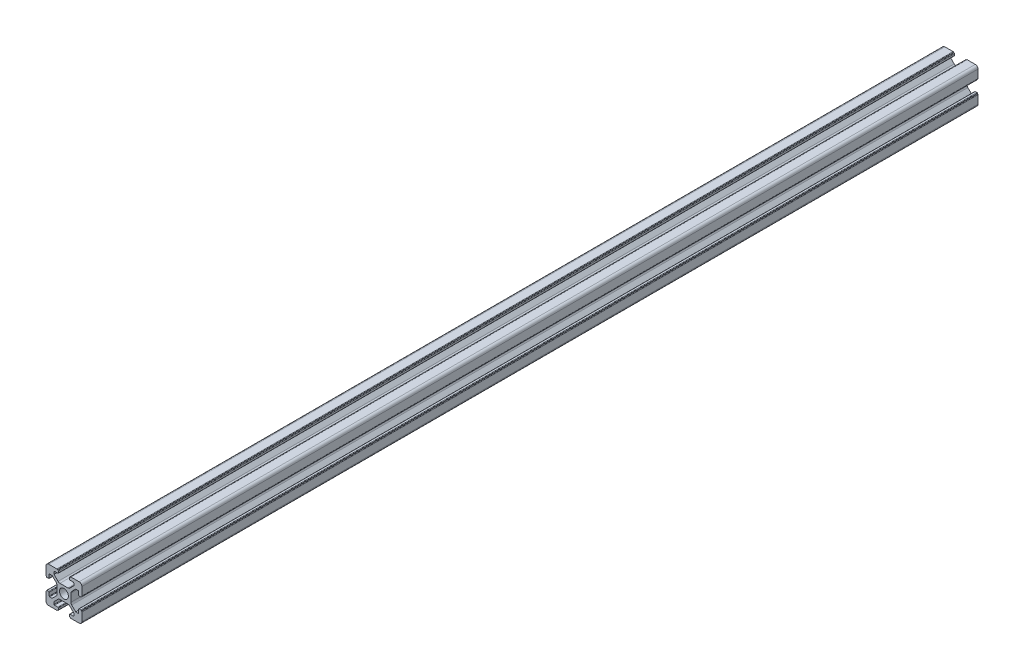
SolidWorks part; units mm, degrees
material "1060 Alloy"
ref_plane "Front Plane" through (0, 0, 0) normal (0, 0, 1) x (1, 0, 0)
ref_plane "Top Plane" through (0, 0, 0) normal (0, 1, 0) x (1, 0, 0)
ref_plane "Right Plane" through (0, 0, 0) normal (1, 0, 0) x (0, 0, -1)
sketch "Sketch1" plane through (0, 0, 0) normal (0, 0, 1) x (1, 0, 0)
  line L0 (3.8995, 3.9005) -> (10.4604, 10.4604) construction
  line L2 (-3.9002, 2.2177) -> (-3.9002, -2.2208)
  line L5 (-3.9005, 3.899) -> (3.9001, -3.8986) construction
  line L6 (-3.9, -3.901) -> (3.8995, 3.9005) construction
  line L7 (-0.0002, 10) -> (-0.0002, -9.9996) construction
  line L8 (-0.0002, -9.9996) -> (-0.0002, 10) construction
  line L9 (5.5006, 6.5619) -> (3.2793, 4.3405)
  line L14 (-10.0002, 9.9996) -> (9.9994, -10) construction
  line L15 (-9.9999, -10.0001) -> (9.9998, 10) construction
  line L16 (6.5613, 5.5012) -> (4.3401, 3.28)
  line L17 (-5.5002, 6.5603) -> (-3.279, 4.3391)
  line L18 (-6.5609, 5.4996) -> (-4.3395, 3.2783)
  line L19 (7.9206, 5.5012) -> (6.5613, 5.5012)
  line L20 (8.2006, 3.3812) -> (8.2006, 5.2212)
  line L21 (9.4206, 3.1012) -> (8.4806, 3.1012)
  line L22 (9.7006, 3.6012) -> (9.7006, 3.3812)
  line L23 (-8.5002, 9.9996) -> (-3.8802, 9.9996)
  line L24 (-3.6002, 9.7196) -> (-3.6002, 9.6996)
  line L25 (-3.6002, 9.6996) -> (-3.3802, 9.6996)
  line L26 (-3.1002, 9.4196) -> (-3.1002, 8.4796)
  line L27 (-3.3802, 8.1996) -> (-5.2202, 8.1996)
  line L28 (-5.5002, 7.9196) -> (-5.5002, 6.5603)
  line L29 (-7.9202, 5.4996) -> (-6.5609, 5.4996)
  line L30 (-8.2002, 3.3796) -> (-8.2002, 5.2196)
  line L31 (-9.4202, 3.0996) -> (-8.4802, 3.0996)
  line L32 (-9.7202, 3.5996) -> (-9.7002, 3.5996)
  line L33 (-9.7002, 3.5996) -> (-9.7002, 3.3796)
  line L34 (-10.0002, 8.4996) -> (-10.0002, 3.8796)
  line L35 (10.0006, 8.5012) -> (10.0006, 3.8812)
  line L36 (8.5006, 10.0012) -> (3.8806, 10.0012)
  line L37 (3.6006, 9.7012) -> (3.3806, 9.7012)
  line L38 (3.1006, 9.4212) -> (3.1006, 8.4812)
  line L39 (3.3806, 8.2012) -> (5.2206, 8.2012)
  line L40 (5.5006, 7.9212) -> (5.5006, 6.5619)
  line L41 (6.5629, -5.4996) -> (4.3415, -3.2783)
  line L42 (5.5022, -6.5603) -> (3.281, -4.3391)
  line L43 (5.5022, -7.9196) -> (5.5022, -6.5603)
  line L44 (3.3822, -8.1996) -> (5.2222, -8.1996)
  line L45 (3.1022, -9.4196) -> (3.1022, -8.4796)
  line L46 (3.6022, -9.6996) -> (3.3822, -9.6996)
  line L47 (8.5022, -9.9996) -> (3.8822, -9.9996)
  line L48 (10.0022, -8.4996) -> (10.0022, -3.8796)
  line L49 (9.7022, -3.5996) -> (9.7022, -3.3796)
  line L50 (9.4222, -3.0996) -> (8.4822, -3.0996)
  line L51 (8.2022, -3.3796) -> (8.2022, -5.2196)
  line L52 (7.9222, -5.4996) -> (6.5629, -5.4996)
  line L53 (-5.4986, -6.5619) -> (-3.2773, -4.3405)
  line L54 (-6.5593, -5.5012) -> (-4.3395, -3.2814)
  line L55 (-7.9186, -5.5012) -> (-6.5593, -5.5012)
  line L56 (-8.1986, -3.3812) -> (-8.1986, -5.2212)
  line L57 (-9.4186, -3.1012) -> (-8.4786, -3.1012)
  line L58 (-9.6986, -3.6012) -> (-9.6986, -3.3812)
  line L59 (-9.9986, -8.5012) -> (-9.9986, -3.8812)
  line L60 (-8.4986, -10.0012) -> (-3.8786, -10.0012)
  line L61 (-3.5986, -9.7012) -> (-3.3786, -9.7012)
  line L62 (-3.0986, -9.4212) -> (-3.0986, -8.4812)
  line L63 (-3.3786, -8.2012) -> (-5.2186, -8.2012)
  line L64 (-5.4986, -7.9212) -> (-5.4986, -6.5619)
  line L65 (-2.233, 3.8998) -> (2.2187, 3.9012)
  line L66 (3.9008, 2.234) -> (3.9022, -2.2177)
  line L67 (2.235, -3.8998) -> (-2.2167, -3.9012)
  line L68 (3.6006, 9.7212) -> (3.6006, 9.6996)
  line L69 (9.7006, 3.6012) -> (9.7206, 3.6012)
  line L70 (-9.6986, -3.6012) -> (-9.7186, -3.6012)
  line L71 (-3.5986, -9.7012) -> (-3.5986, -9.7212)
  line L72 (3.6022, -9.6996) -> (3.6022, -9.7196)
  line L73 (9.7222, -3.5996) -> (9.7022, -3.5996)
  arc A0 (-3.6002, 9.7196) -> (-3.8802, 9.9996) centre (-3.8802, 9.7196) ccw
  arc A1 (-3.3802, 9.6996) -> (-3.1002, 9.4196) centre (-3.3802, 9.4196) cw
  arc A2 (-3.1002, 8.4796) -> (-3.3802, 8.1996) centre (-3.3802, 8.4796) cw
  arc A3 (-10.0002, 8.4996) -> (-8.5002, 9.9996) centre (-8.5002, 8.4996) cw
  arc A4 (-8.2002, 3.3796) -> (-8.4802, 3.0996) centre (-8.4802, 3.3796) cw
  arc A5 (-9.4202, 3.0996) -> (-9.7002, 3.3796) centre (-9.4202, 3.3796) cw
  arc A6 (-9.7202, 3.5996) -> (-10.0002, 3.8796) centre (-9.7202, 3.8796) cw
  arc A7 (-3.279, 4.3391) -> (-2.233, 3.8998) centre (-2.2183, 5.3997) ccw
  arc A8 (-4.3395, 3.2783) -> (-3.9002, 2.2177) centre (-5.4002, 2.2177) cw
  arc A9 (-7.9202, 5.4996) -> (-8.2002, 5.2196) centre (-7.9202, 5.2196) ccw
  arc A10 (-5.2202, 8.1996) -> (-5.5002, 7.9196) centre (-5.2202, 7.9196) ccw
  arc A12 (-4.3395, -3.2814) -> (-3.9002, -2.2208) centre (-5.4002, -2.2208) ccw
  arc A13 (8.2006, 5.2212) -> (7.9206, 5.5012) centre (7.9206, 5.2212) ccw
  arc A14 (8.4806, 3.1012) -> (8.2006, 3.3812) centre (8.4806, 3.3812) cw
  arc A15 (9.7006, 3.3812) -> (9.4206, 3.1012) centre (9.4206, 3.3812) cw
  arc A16 (9.7206, 3.6012) -> (10.0006, 3.8812) centre (9.7206, 3.8812) ccw
  arc A17 (8.5006, 10.0012) -> (10.0006, 8.5012) centre (8.5006, 8.5012) cw
  arc A18 (3.6006, 9.7212) -> (3.8806, 10.0012) centre (3.8806, 9.7212) cw
  arc A19 (3.1006, 9.4212) -> (3.3806, 9.7012) centre (3.3806, 9.4212) cw
  arc A20 (3.3806, 8.2012) -> (3.1006, 8.4812) centre (3.3806, 8.4812) cw
  arc A21 (5.5006, 7.9212) -> (5.2206, 8.2012) centre (5.2206, 7.9212) ccw
  arc A22 (3.2793, 4.3405) -> (2.2187, 3.9012) centre (2.2187, 5.4012) cw
  arc A23 (4.3401, 3.28) -> (3.9008, 2.234) centre (5.4007, 2.2193) ccw
  arc A25 (5.2222, -8.1996) -> (5.5022, -7.9196) centre (5.2222, -7.9196) ccw
  arc A26 (3.1022, -8.4796) -> (3.3822, -8.1996) centre (3.3822, -8.4796) cw
  arc A27 (3.3822, -9.6996) -> (3.1022, -9.4196) centre (3.3822, -9.4196) cw
  arc A28 (3.6022, -9.7196) -> (3.8822, -9.9996) centre (3.8822, -9.7196) ccw
  arc A29 (10.0022, -8.4996) -> (8.5022, -9.9996) centre (8.5022, -8.4996) cw
  arc A30 (9.7222, -3.5996) -> (10.0022, -3.8796) centre (9.7222, -3.8796) cw
  arc A31 (9.4222, -3.0996) -> (9.7022, -3.3796) centre (9.4222, -3.3796) cw
  arc A32 (8.2022, -3.3796) -> (8.4822, -3.0996) centre (8.4822, -3.3796) cw
  arc A33 (7.9222, -5.4996) -> (8.2022, -5.2196) centre (7.9222, -5.2196) ccw
  arc A34 (4.3415, -3.2783) -> (3.9022, -2.2177) centre (5.4022, -2.2177) cw
  arc A35 (3.281, -4.3391) -> (2.235, -3.8998) centre (2.2203, -5.3997) ccw
  circle A36 centre (0.001, -0.001) radius 2.5 construction
  arc A37 (-8.1986, -5.2212) -> (-7.9186, -5.5012) centre (-7.9186, -5.2212) ccw
  arc A38 (-8.4786, -3.1012) -> (-8.1986, -3.3812) centre (-8.4786, -3.3812) cw
  arc A39 (-9.6986, -3.3812) -> (-9.4186, -3.1012) centre (-9.4186, -3.3812) cw
  arc A40 (-9.7186, -3.6012) -> (-9.9986, -3.8812) centre (-9.7186, -3.8812) ccw
  arc A41 (-8.4986, -10.0012) -> (-9.9986, -8.5012) centre (-8.4986, -8.5012) cw
  arc A42 (-3.5986, -9.7212) -> (-3.8786, -10.0012) centre (-3.8786, -9.7212) cw
  arc A43 (-3.0986, -9.4212) -> (-3.3786, -9.7012) centre (-3.3786, -9.4212) cw
  arc A44 (-3.3786, -8.2012) -> (-3.0986, -8.4812) centre (-3.3786, -8.4812) cw
  arc A45 (-5.4986, -7.9212) -> (-5.2186, -8.2012) centre (-5.2186, -7.9212) ccw
  arc A46 (-3.2773, -4.3405) -> (-2.2167, -3.9012) centre (-2.2167, -5.4012) cw
  arc A48 (-4.3381, -3.28) -> (-3.8988, -2.234) centre (-5.3987, -2.2193) ccw [skipped]
  point P0 (0, 0)
  point P9 (-0.0002, 0.0002)
  point P12 (-0.0003, -0.0003)
  point P43 (-3.6002, 9.9996)
  point P46 (-3.1002, 9.6996)
  point P49 (-3.1002, 8.1996)
  point P55 (-8.2002, 3.0996)
  point P58 (-9.7002, 3.0996)
  point P61 (-10.0002, 3.5996)
  point P64 (-2.8395, 3.8996)
  point P67 (-3.9002, 2.839)
  point P70 (-8.2002, 5.4996)
  point P73 (-5.5002, 8.1996)
  point P184 (0.001, 0)
  dimension "D14" = 0.28
  dimension "D15" = 0.28
  dimension "D16" = 0.28
  dimension "D17" = 1.5
  dimension "D18" = 0.28
  dimension "D19" = 1.5
  dimension "D20" = 1.5
  dimension "D21" = 0.28
  dimension "D23" = 5
  dimension "D27" = 1.5
  dimension "D1" = 7.8
  dimension "D2" = 7.8
  dimension "D3" = 3.1
  dimension "D4" = 3.6
  dimension "D5" = 20
  dimension "D6" = 20
  dimension "D7" = 0.75
  dimension "D8" = 1.8
  dimension "D9" = 5.5
  dimension "D10" = 6.4
  dimension "D11" = 6.4
  dimension "D12" = 3.7627
  dimension "D13" = 0.3
  dimension "D24" = 4.62
  dimension "D25" = 3.9005
  dimension "D26" = 7.801
  dimension "D22" = 4
extrude "Boss-Extrude1" add sketch "Sketch1" along normal blind 500 contours L53 A46 L67 A35 L42 L43 A25 L44 A26 L45 A27 L46 L72 A28 L47 A29 L48 A30 L73 L49 A31 L50 A32 L51 A33 L52 L41 A34 L66 A23 L16 L19 A13 L20 A14 L21 A15 L22 L69 A16 L35 A17 L36 A18 L68 L37 A19 L38 A20 region at (0.0009, 0, 0)
sketch3d "3DSketch2"
  circle A0 centre (0, 0, 0) radius 2.5
  point P2 (0, 0, 2.5)
extrude "Cut-Extrude1" cut sketch "3DSketch2" along direction (0, 0, 1) on the side of the normal through all contours A0
